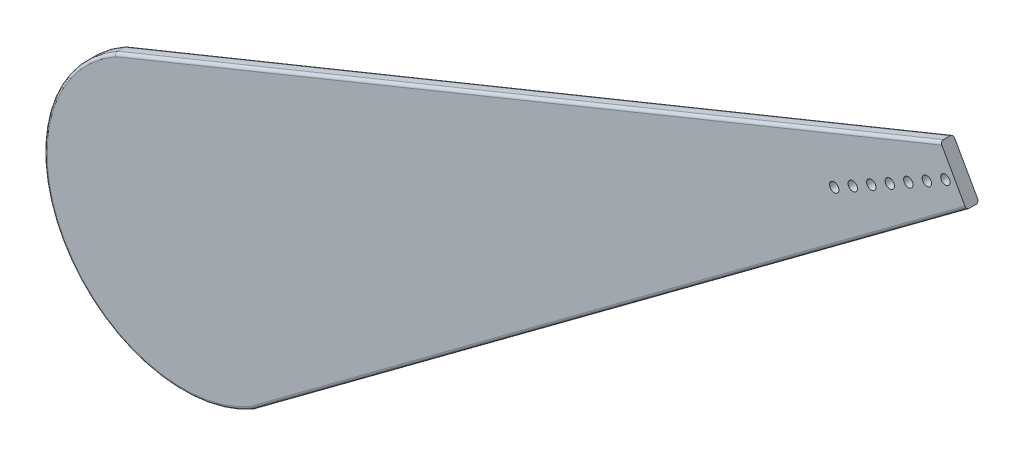
SolidWorks part; units mm, degrees
ref_plane "前视基准面" through (0, 0, 0) normal (0, 0, 1) x (1, 0, 0)
ref_plane "上视基准面" through (0, 0, 0) normal (0, 1, 0) x (1, 0, 0)
ref_plane "右视基准面" through (0, 0, 0) normal (1, 0, 0) x (0, 0, -1)
other "Configuration Table"
sketch "草图1" plane through (0, 0, 0) normal (0, 0, 1) x (1, 0, 0)
  line L0 (0, -55) -> (0, 55) construction
  line L1 (0, 5) -> (50, 5)
  line L3 (0, -5) -> (50, -5)
  line L5 (55, 0) -> (-55, 0) construction
  line L13 (0, -5) -> (-176.616, -136.1747)
  line L14 (-5, 3.6603) -> (-208.7523, -79.3156)
  arc A0 (50, -5) -> (50, 5) centre (50, 0) ccw
  arc A3 (0, 5) -> (-5, 3.6603) centre (0, -5) ccw
  arc A7 (-208.7523, -79.3156) -> (-176.616, -136.1747) centre (-192.6841, -107.7451) ccw
  dimension "D4" = 5
  dimension "D9" = 220
  dimension "D7" = 5
  dimension "D10" = 5
  dimension "D5" = 220
  dimension "D11" = 32.6562
  dimension "D1" = 50
  dimension "D2" = 10
  dimension "D3" = 5
  dimension "D6" = 202.158
  dimension "D8" = 143.398
extrude "凸台-拉伸1" add sketch "草图1" along normal blind 3
sketch "草图3" plane through (0, 0, 3) normal (0, 0, 1) x (1, 0, 0)
  line L1 (5, 1.1) -> (50, 1.1)
  line L3 (5, -1.1) -> (50, -1.1)
  line L5 (55, 0) -> (-55, 0) construction
  line L6 (0, -55) -> (0, 55) construction
  arc A0 (50, -1.1) -> (50, 1.1) centre (50, 0) ccw
  arc A1 (5, 1.1) -> (5, -1.1) centre (5, 0) ccw
  dimension "D5" = 45
  dimension "D1" = 1.1
  dimension "D4" = 1.1
  dimension "D2" = 2.2
  dimension "D3" = 1.1
  dimension "D6" = 5
  dimension "D7" = 5
extrude "切除-拉伸1" cut sketch "草图3" against normal blind 3
sketch "草图4" plane through (0, 0, 3) normal (0, 0, 1) x (1, 0, 0)
  line L0 (0, 0) -> (-221.1137, -123.8133)
  arc A1 (-208.7523, -79.3156) -> (-176.616, -136.1747) centre (-192.6841, -107.7451) ccw construction
ref_plane "基准面1" through (0, 0, 0) normal (-0.4886, 0.8725, 0) x (-0.8725, -0.4886, 0)
hole_wizard "Ø2.2 (2.2) 直径孔1" positions "草图7" profile "草图8" hole size "Ø2.2" standard "ANSI Metric" end condition up to next
sketch "草图7" plane through (0, 0, 3) normal (0, 0, 1) x (1, 0, 0)
  line L0 (0, 0) -> (-221.1137, -123.8133) construction
  line L1 (0, -1.65) -> (0, 1.65) construction
  point P1 (0, 0)
  dimension "D1" = 0
sketch "草图8" plane through (0, 0, 3) normal (1, 0, 0) x (0, -1, 0)
  line L0 (0, 0) -> (0, 3)
  line L1 (0, 3) -> (1.1, 3)
  line L2 (1.1, 3) -> (1.1, 0)
  line L5 (1.1, 0) -> (0, 0)
  line L11 (0, -6.35) -> (0, 107.95) construction
  dimension "通孔孔直径" = 2.2
  dimension "通孔孔深度" = 3
pattern_linear "阵列(线性)1" count 10 spacing 5 along (-0.8725, -0.4886, 0) of "Ø2.2 (2.2) 直径孔1"
fillet "圆角1" radius 0.7 14 edges at (55, 0, 0) (55, 0, 3) (25, 5, 3) (-2.5882, 4.6593, 3) (-2.5882, 4.6593, 0) (25, 5, 0) (25, -5, 0) (25, -5, 3) (-106.8762, -37.8277, 3) (-106.8762, -37.8277, 0) (-88.308, -70.5873, 0) (-88.308, -70.5873, 3) (-221.1137, -123.8133, 0) (-221.1137, -123.8133, 3)
sketch "草图9" plane through (0, 0, 3) normal (0, 0, 1) x (1, 0, 0)
  line L0 (125.6956, 70.3837) -> (-125.6956, -70.3837) construction
  line L4 (-19.2123, 8.7257) -> (56.1701, 9.8861)
  line L5 (-10.9065, -6.1072) -> (-7.2455, -12.6453)
  line L6 (-10.9065, -6.1072) -> (-19.2123, 8.7257)
  line L8 (56.1701, 9.8861) -> (56.1701, -8.8723)
  line L9 (56.1701, -8.8723) -> (-7.2455, -12.6453)
  dimension "D1" = 17
  dimension "D2" = 90
  dimension "D3" = 61.635
  dimension "D4" = 18.7584
  dimension "D5" = 56.1701
  dimension "D7" = 7.4934
  dimension "D8" = 90
  dimension "D9" = 12.5
  dimension "D10" = 10.9065
extrude "切除-拉伸2" cut sketch "草图9" against normal through all
